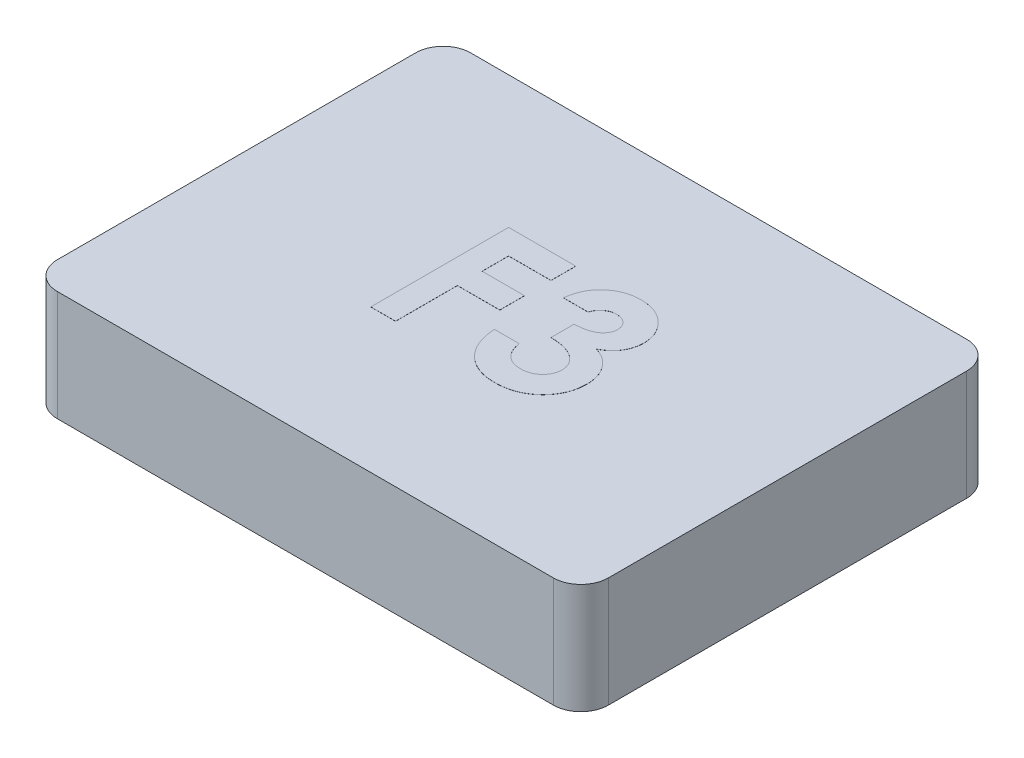
SolidWorks part; units mm, degrees
ref_plane "Front Plane" through (0, 0, 0) normal (0, 0, 1) x (1, 0, 0)
ref_plane "Top Plane" through (0, 0, 0) normal (0, 1, 0) x (1, 0, 0)
ref_plane "Right Plane" through (0, 0, 0) normal (1, 0, 0) x (0, 0, -1)
sketch "Sketch1" plane through (0, 0, 0) normal (0, 1, 0) x (1, 0, 0)
  line L0 (0, 0) -> (12.7, 0)
  line L1 (12.7, 0) -> (12.7, 9.525)
  line L2 (12.7, 9.525) -> (0, 9.525)
  line L3 (0, 9.525) -> (0, 0)
  dimension "D1" = 12.7
  dimension "D2" = 9.525
extrude "Boss-Extrude1" add sketch "Sketch1" along normal blind 2.54
fillet "Fillet1" radius 0.635 4 edges at (0, 1.27, -9.525) (12.7, 1.27, -9.525) (12.7, 1.27, 0) (0, 1.27, 0)
shell "Shell1" thickness 0.635 removed face at (6.35, 0, -4.7625)
sketch "Sketch2" plane through (0, 1.905, 0) normal (0, -1, 0) x (-1, 0, 0)
  line L0 (-0.635, 4.7625) -> (-12.065, 4.7625) construction
  line L1 (-0.635, 8.89) -> (-0.635, 0.635) construction
  line L2 (-12.065, 0.635) -> (-12.065, 8.89) construction
  line L3 (-6.35, 0.635) -> (-6.35, 8.89) construction
  line L4 (-0.635, 0.635) -> (-12.065, 0.635) construction
  line L5 (-12.065, 8.89) -> (-0.635, 8.89) construction
  circle A0 centre (-6.35, 4.7625) radius 2.54
  dimension "D1" = 5.08
extrude "Boss-Extrude2" add sketch "Sketch2" along normal up to surface (1.905 mm away) up to face at (6.35, 0, -4.7625)
sketch "Sketch3" plane through (0, 2.54, 0) normal (0, 1, 0) x (1, 0, 0)
  line L0 (0.635, 0) -> (12.065, 0) construction
  line L1 (0, 8.89) -> (0, 0.635) construction
  text T0 "<b>F3</b>"
  dimension "D1" = 3.302
  dimension "D2" = 4.191
extrude "Boss-Extrude3" add sketch "Sketch3" along normal blind 0.0025
